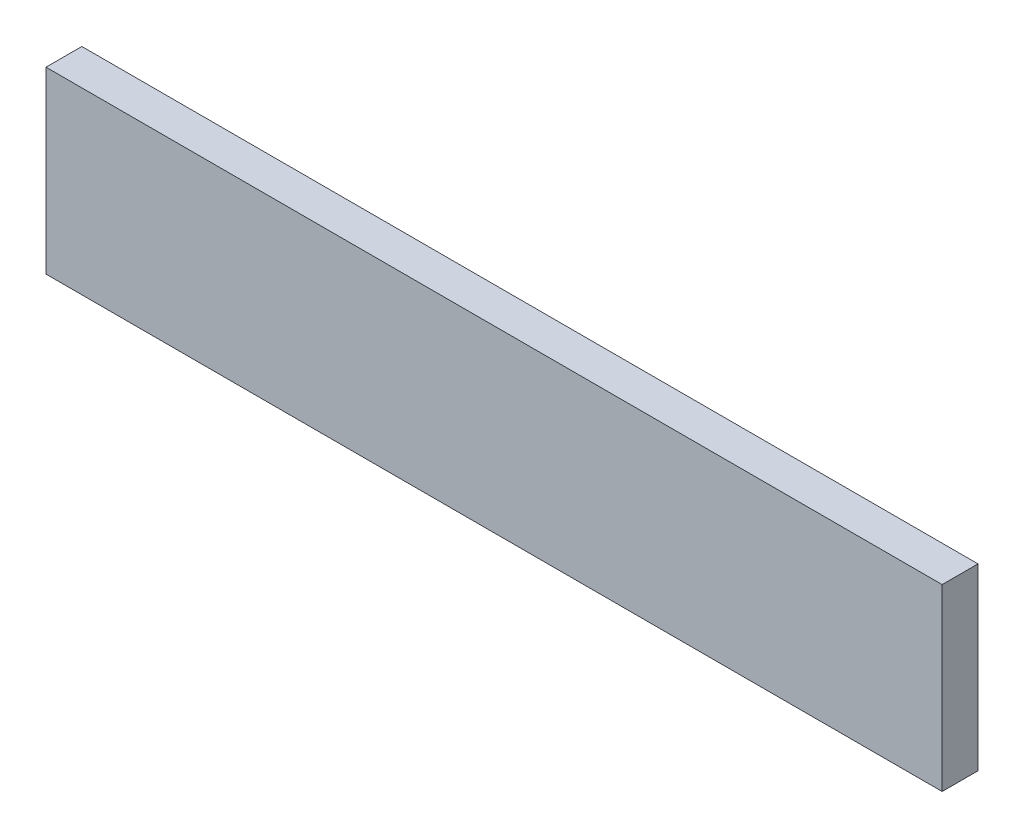
SolidWorks part; units mm, degrees
ref_plane "Front Plane" through (0, 0, 0) normal (0, 0, 1) x (1, 0, 0)
ref_plane "Top Plane" through (0, 0, 0) normal (0, 1, 0) x (1, 0, 0)
ref_plane "Right Plane" through (0, 0, 0) normal (1, 0, 0) x (0, 0, -1)
sketch "Sketch1" plane through (0, 0, 0) normal (0, 0, 1) x (1, 0, 0)
  line L1 (0, 0) -> (150, 0)
  line L2 (0, 0) -> (0, 30)
  line L3 (0, 30) -> (150, 30)
  line L4 (150, 0) -> (150, 30)
  dimension "D1" = 30
  dimension "D2" = 150
extrude "Boss-Extrude1" add sketch "Sketch1" along normal blind 6
